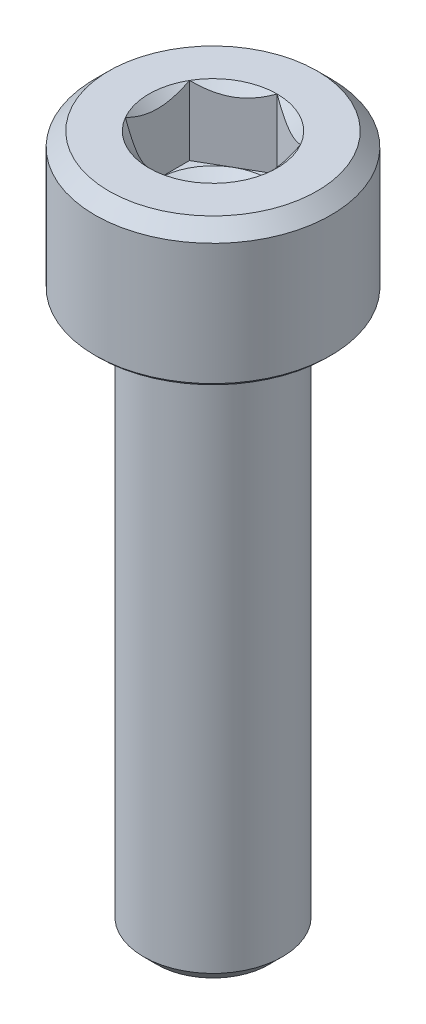
SolidWorks part; units mm, degrees
ref_plane "Front Plane" through (0, 0, 0) normal (0, 0, 1) x (1, 0, 0)
ref_plane "Top Plane" through (0, 0, 0) normal (0, 1, 0) x (1, 0, 0)
ref_plane "Right Plane" through (0, 0, 0) normal (1, 0, 0) x (0, 0, -1)
sketch "Sketch1" plane through (0, 0, 0) normal (0, 0, 1) x (1, 0, 0)
  line L0 (0, 1.3453) -> (2, 2.5)
  line L1 (2, 2.5) -> (2, 4.6906)
  line L2 (2, 4.6906) -> (2.3094, 5)
  line L3 (2.3094, 5) -> (3.75, 5)
  line L4 (3.75, 5) -> (4.25, 4.5)
  line L5 (4.25, 4.5) -> (4.25, 0.125)
  line L6 (4.25, 0.125) -> (4.125, 0)
  line L7 (4.125, 0) -> (2.55, 0)
  line L8 (2.55, 0) -> (2.5, -0.6)
  line L9 (2.5, -0.6) -> (2.5, -19.5095)
  line L10 (2.5, -19.5095) -> (2.0095, -20)
  line L11 (2.0095, -20) -> (0, -20)
  line L12 (0, -20) -> (0, 1.3453)
  line L13 (0, -20) -> (0, 5) construction
revolve "Revolve1" add sketch "Sketch1" angle 360 about L13 reverse direction yes
cosmetic thread "Cosmetic Thread1" parameters "D1"=17.6, "D2"=4.019
ref_plane "Plane1" through (0, 5, 0) normal (0, 1, 0) x (1, 0, 0)
sketch "Sketch2" plane through (0, 5, 0) normal (0, 1, 0) x (1, 0, 0)
  line L0 (-2, -1.1547) -> (0, -2.3094)
  line L1 (0, -2.3094) -> (2, -1.1547)
  line L2 (2, -1.1547) -> (2, 1.1547)
  line L3 (2, 1.1547) -> (0, 2.3094)
  line L4 (0, 2.3094) -> (-2, 1.1547)
  line L5 (-2, 1.1547) -> (-2, -1.1547)
extrude "Cut-Extrude1" cut sketch "Sketch2" against normal blind 2.5
ref_plane "Plane2" through (0, -20, 0) normal (0, 1, 0) x (1, 0, 0)
ref_plane "ANBAU XY" through (0, 0, 0) normal (0, 1, 0) x (1, 0, 0)
ref_plane "ANBAU XZ" through (0, 0, 0) normal (0, 0, 1) x (1, 0, 0)
ref_plane "ANBAU YZ" through (0, 0, 0) normal (1, 0, 0) x (0, 0, -1)
ref_axis "ANBAU X" through (-80.9, 0, 0) along (1, 0, 0)
ref_axis "ANBAU Y" through (0, 0, 50) along (0, 0, -1)
ref_axis "ANBAU Z" through (0, 50, 0) along (0, -1, 0)
sketch3d "ANBAU"
  point P0 (0, 0, 0)
ref_plane "Schraube XY" through (0, 0, 0) normal (0, 1, 0) x (1, 0, 0)
ref_plane "Schraube XZ" through (0, 0, 0) normal (0, 0, 1) x (1, 0, 0)
ref_plane "Schraube YZ" through (0, 0, 0) normal (1, 0, 0) x (0, 0, -1)
ref_axis "Schraube X" through (-80.9, 0, 0) along (1, 0, 0)
ref_axis "Schraube Y" through (0, 0, 50) along (0, 0, -1)
ref_axis "Schraube Z" through (0, 50, 0) along (0, -1, 0)
sketch3d "Schraube"
  point P0 (0, 0, 0)
ref_plane "insert XY" through (0, 0, 0) normal (0, 1, 0) x (1, 0, 0)
ref_plane "insert XZ" through (0, 0, 0) normal (0, 0, 1) x (1, 0, 0)
ref_plane "insert YZ" through (0, 0, 0) normal (1, 0, 0) x (0, 0, -1)
ref_axis "insert X" through (-80.9, 0, 0) along (1, 0, 0)
ref_axis "insert Y" through (0, 0, 50) along (0, 0, -1)
ref_axis "insert Z" through (0, 50, 0) along (0, -1, 0)
sketch3d "insert"
  point P0 (0, 0, 0)
ref_plane "schrauben_punkt XY" through (0, -20, 0) normal (0, 1, 0) x (1, 0, 0)
ref_plane "schrauben_punkt XZ" through (0, 0, 0) normal (0, 0, 1) x (1, 0, 0)
ref_plane "schrauben_punkt YZ" through (0, 0, 0) normal (1, 0, 0) x (0, 0, -1)
ref_axis "schrauben_punkt X" through (-80.9, -20, 0) along (1, 0, 0)
ref_axis "schrauben_punkt Y" through (0, -20, 50) along (0, 0, -1)
ref_axis "schrauben_punkt Z" through (0, 50, 0) along (0, -1, 0)
sketch3d "schrauben_punkt"
  point P0 (0, -20, 0)
other "Freeze***"
